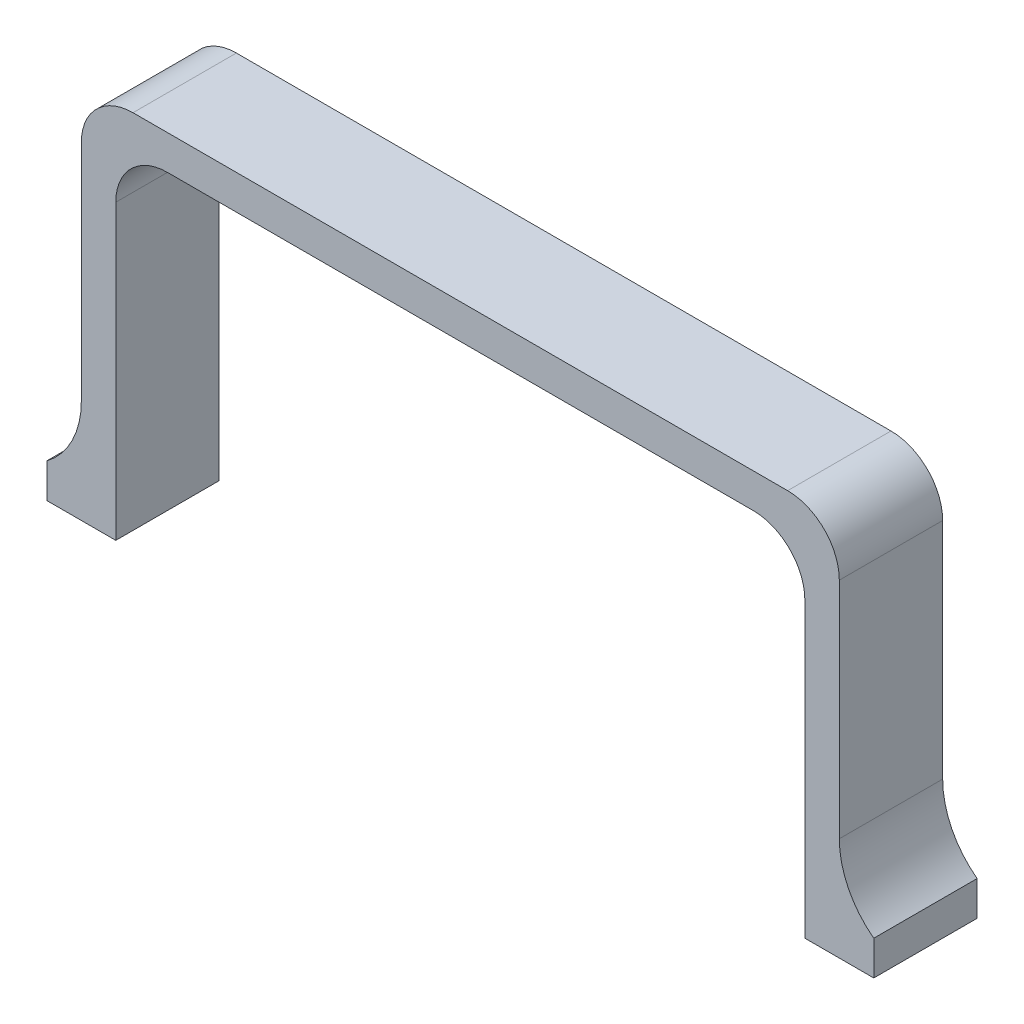
SolidWorks part; units mm, degrees
ref_plane "前视基准面" through (0, 0, 0) normal (0, 0, 1) x (1, 0, 0)
ref_plane "上视基准面" through (0, 0, 0) normal (0, 1, 0) x (1, 0, 0)
ref_plane "右视基准面" through (0, 0, 0) normal (1, 0, 0) x (0, 0, -1)
sketch "草图1" plane through (0, 0, 0) normal (0, 0, 1) x (1, 0, 0)
  line L0 (0, 31.5815) -> (0, -26.9744) construction
  line L1 (-20, 0) -> (20, 0)
  line L2 (20, 0) -> (20, -20)
  line L3 (20, -20) -> (24, -20)
  line L4 (24, -20) -> (24, -18)
  line L5 (24, -18) -> (22, -18)
  line L6 (22, -18) -> (22, 2)
  line L7 (22, 2) -> (-22, 2)
  line L8 (-22, -18) -> (-22, 2)
  line L9 (-24, -18) -> (-22, -18)
  line L10 (-24, -20) -> (-24, -18)
  line L11 (-20, -20) -> (-24, -20)
  line L12 (-20, 0) -> (-20, -20)
  point P12 (0, 2)
  point P17 (0, 0)
  dimension "D1" = 40
  dimension "D2" = 20
  dimension "D3" = 2
  dimension "D4" = 2
  dimension "D5" = 2
  dimension "D6" = 4
extrude "凸台-拉伸1" add sketch "草图1" along normal blind 6
fillet "圆角1" radius 5 2 edges at (22, -18, 3) (-22, -18, 3)
fillet "圆角2" radius 3 4 edges at (22, 2, 3) (20, 0, 3) (-20, 0, 3) (-22, 2, 3)
